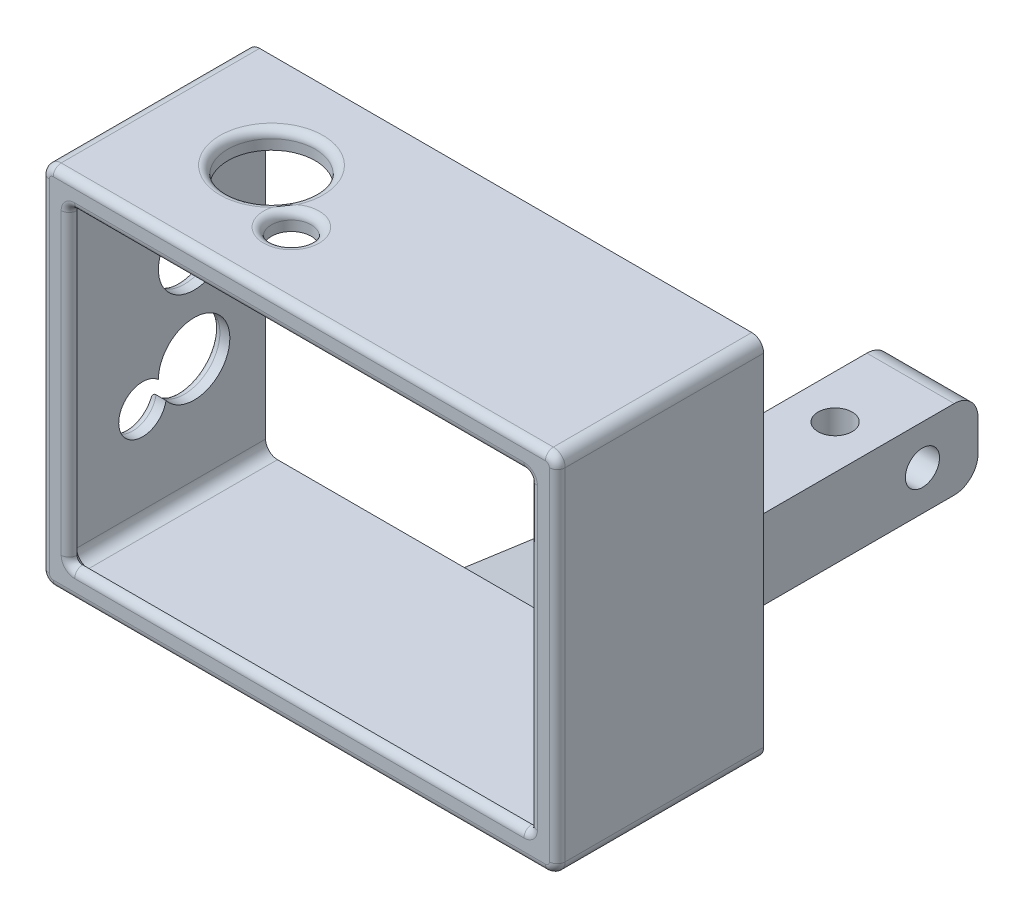
SolidWorks part; units mm, degrees
ref_plane "Front Plane" through (0, 0, 0) normal (0, 0, 1) x (1, 0, 0)
ref_plane "Top Plane" through (0, 0, 0) normal (0, 1, 0) x (1, 0, 0)
ref_plane "Right Plane" through (0, 0, 0) normal (1, 0, 0) x (0, 0, -1)
sketch "Sketch1" plane through (0, 0, 0) normal (0, 0, 1) x (1, 0, 0)
  line L1 (-32.5, 23) -> (32.5, 23)
  line L2 (-32.5, 23) -> (-32.5, -23)
  line L3 (-32.5, -23) -> (32.5, -23)
  line L4 (32.5, 23) -> (32.5, -23)
  line L5 (-32.5, 23) -> (32.5, -23) construction
  line L6 (-32.5, -23) -> (32.5, 23) construction
  point P0 (0, 0)
  dimension "D1" = 65
  dimension "D2" = 46
extrude "Boss-Extrude1" add sketch "Sketch1" along normal blind 26
sketch "Sketch2" plane through (0, 0, 0) normal (0, 0, -1) x (-1, 0, 0)
  line L1 (-30.25, 20.75) -> (30.25, 20.75)
  line L2 (-30.25, 20.75) -> (-30.25, -20.75)
  line L3 (-30.25, -20.75) -> (30.25, -20.75)
  line L4 (30.25, 20.75) -> (30.25, -20.75)
  line L5 (-30.25, 20.75) -> (30.25, -20.75) construction
  line L6 (-30.25, -20.75) -> (30.25, 20.75) construction
  point P0 (0, 0)
  dimension "D1" = 60.5
  dimension "D2" = 41.5
extrude "Cut-Extrude1" cut sketch "Sketch2" against normal blind 25
sketch "Sketch3" plane through (0, 0, 25) normal (0, 0, -1) x (-1, 0, 0)
  line L1 (-29, 19.5) -> (29, 19.5)
  line L2 (-29, 19.5) -> (-29, -19.5)
  line L3 (-29, -19.5) -> (29, -19.5)
  line L4 (29, 19.5) -> (29, -19.5)
  line L5 (-29, 19.5) -> (29, -19.5) construction
  line L6 (-29, -19.5) -> (29, 19.5) construction
  point P0 (0, 0)
  dimension "D1" = 58
  dimension "D2" = 39
extrude "Cut-Extrude2" cut sketch "Sketch3" against normal blind 2
sketch "Sketch4" plane through (0, 23, 0) normal (0, 1, 0) x (1, 0, 0)
  line L2 (32.5, 0) -> (-32.5, 0) construction
  line L3 (-30.25, -25) -> (-30.25, 0) construction
  circle A0 centre (-17.5, -12) radius 5.5
  dimension "D3" = 11
  dimension "D1" = 12.75
  dimension "D2" = 12
extrude "Cut-Extrude3" cut sketch "Sketch4" against normal blind 3
sketch "Sketch6" plane through (-32.5, 0, 0) normal (-1, 0, 0) x (0, 0, 1)
  line L0 (0, 23) -> (0, -23) construction
  circle A0 centre (9, 6) radius 4.5
  circle A1 centre (9, -6) radius 4.5
  dimension "D1" = 9
  dimension "D2" = 9
  dimension "D3" = 12
  dimension "D4" = 6
  dimension "D5" = 9
extrude "Cut-Extrude4" cut sketch "Sketch6" against normal blind 2.5
sketch "Sketch7" plane through (-32.5, 0, 0) normal (-1, 0, 0) x (0, 0, 1)
  line L0 (25, -20.75) -> (0, -20.75) construction
  line L1 (0, 23) -> (0, -23) construction
  circle A0 centre (15.5, -8.25) radius 3
  dimension "D1" = 6
  dimension "D2" = 12.5
  dimension "D3" = 15.5
extrude "Cut-Extrude5" cut sketch "Sketch7" against normal blind 2.5
sketch "Sketch8" plane through (0, 23, 0) normal (0, 1, 0) x (1, 0, 0)
  line L0 (-30.25, -25) -> (-30.25, 0) construction
  line L1 (32.5, 0) -> (-32.5, 0) construction
  circle A0 centre (-9.5, -17.5) radius 2.5
  dimension "D3" = 5
  dimension "D1" = 20.75
  dimension "D2" = 17.5
extrude "Cut-Extrude6" cut sketch "Sketch8" against normal blind 2.5
fillet "Fillet1" radius 1 5 edges at (-32.5, -9.2313, 18.335) (-32.5, -4.528, 4.7476) (-32.5, 1.5, 9) (-9.5, 23, 20) (-17.5, 23, 17.5)
fillet "Fillet2" radius 1.5 8 edges at (30.25, -20.75, 12.5) (-30.25, -20.75, 12.5) (-30.25, 20.75, 12.5) (30.25, 20.75, 12.5) (32.5, -23, 13) (32.5, 23, 13) (-32.5, -23, 13) (-32.5, 23, 13)
fillet "Fillet4" radius 0.7 4 edges at (-29, -19.5, 25.5) (29, -19.5, 25.5) (29, 19.5, 25.5) (-29, 19.5, 25.5)
chamfer "Chamfer2" distance 1.2 angle 45 8 edges at (-30.25, 0, 25) (-29.8107, 20.3107, 25) (-29.8107, -20.3107, 25) (0, 20.75, 25) (0, -20.75, 25) (29.8107, 20.3107, 25) (29.8107, -20.3107, 25) (30.25, 0, 25)
sketch "Sketch9" plane through (0, 0, 26) normal (0, 0, 1) x (1, 0, 0)
  line L0 (-31, -23) -> (31, -23) construction
  line L1 (-5.5, -23) -> (5.5, -23)
  line L2 (-5.5, -23) -> (-5.5, -33)
  line L3 (-5.5, -33) -> (5.5, -33)
  line L4 (5.5, -23) -> (5.5, -33)
  line L5 (-5.5, -23) -> (5.5, -33) construction
  line L6 (-5.5, -33) -> (5.5, -23) construction
  point P0 (0, -28)
  dimension "D1" = 11
  dimension "D2" = 10
  dimension "D3" = 0
  dimension "D4" = 0
extrude "Boss-Extrude2" add sketch "Sketch9" against normal blind 80
sketch "Sketch10" plane through (-5.5, 0, 0) normal (-1, 0, 0) x (0, 0, 1)
  line L0 (-54, -23) -> (-54, -33) construction
  line L2 (-54, -23) -> (0, -23) construction
  circle A0 centre (-47, -28) radius 2.15
  dimension "D1" = 4.3
  dimension "D2" = 7
  dimension "D3" = 5
extrude "Cut-Extrude7" cut sketch "Sketch10" against normal blind 11
fillet "Fillet5" radius 3 2 edges at (0, -33, -54) (0, -23, -54)
chamfer "Chamfer4" distance 2 angle 82 1 edges at (0, -23, 0) first distance on face at (0, 0, 0)
sketch "Sketch12" plane through (0, -33, 0) normal (0, -1, 0) x (1, 0, 0)
  line L0 (-5.5, -51) -> (-5.5, 26) construction
  line L1 (5.5, 26) -> (-5.5, 26)
  line L2 (5.5, 26) -> (5.5, 16)
  line L3 (5.5, 16) -> (-5.5, 16)
  line L4 (-5.5, 26) -> (-5.5, 16)
  dimension "D1" = 10
extrude "Cut-Extrude9" cut sketch "Sketch12" against normal blind 10
chamfer "Chamfer5" distance 10 angle 75 1 edges at (0, -33, 16) first distance on face at (0, -28, 16)
fillet "Fillet10" radius 1 16 edges at (28.795, -19.295, 26) (29, 0, 26) (28.795, 19.295, 26) (0, 19.5, 26) (-28.795, 19.295, 26) (-29, 0, 26) (-28.795, -19.295, 26) (0, -19.5, 26) (-32.0607, -22.5607, 26) (-32.5, 0, 26) (-32.0607, 22.5607, 26) (0, 23, 26) (32.0607, 22.5607, 26) (32.5, 0, 26) (32.0607, -22.5607, 26) (0, -23, 26)
sketch "Sketch13" plane through (0, -23, 0) normal (0, 1, 0) x (1, 0, 0)
  line L0 (-5.5, 54) -> (5.5, 54) construction
  circle A0 centre (0, 41.5) radius 2.15
  dimension "D1" = 4.3
  dimension "D2" = 12.5
extrude "Cut-Extrude10" cut sketch "Sketch13" against normal blind 10
fillet "Fillet11" radius 11 2 edges at (0, -23, -14.2307) (0, -33, -21.3205)
